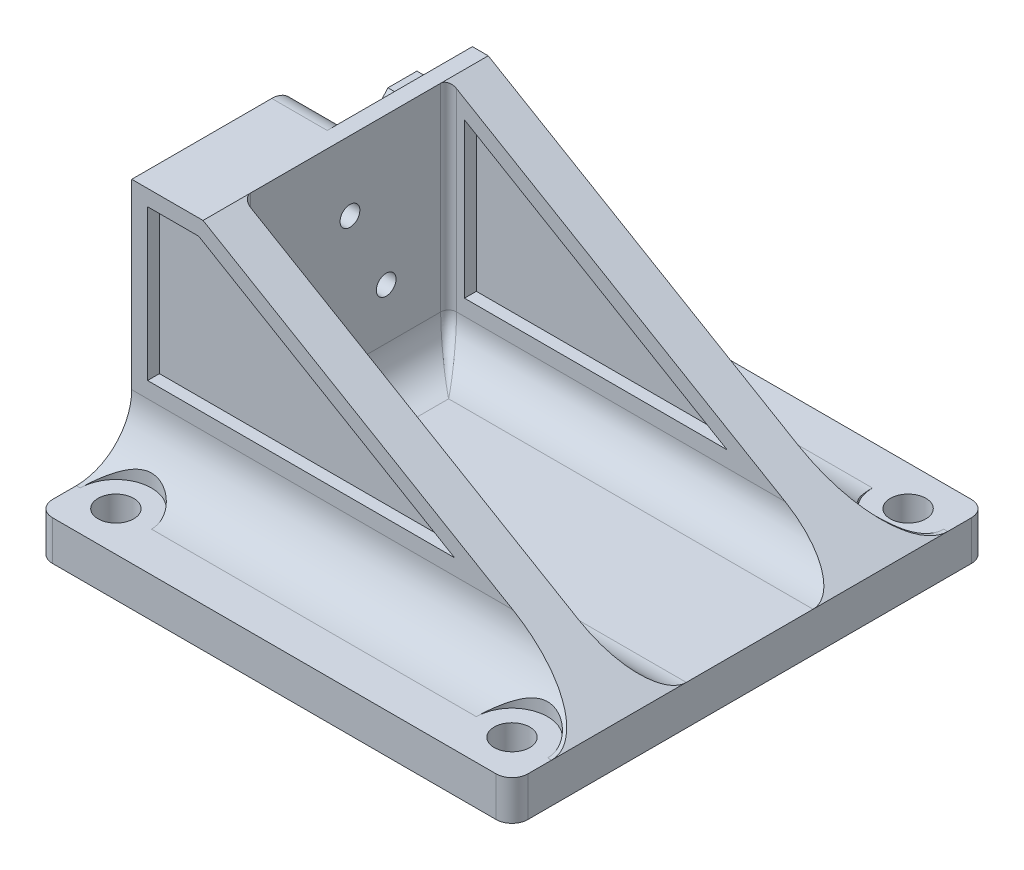
SolidWorks part; units mm, degrees
note: '?' marks a value the reader was unsure of.
ref_plane "Front Plane" through (0, 0, 0) normal (0, 0, 1) x (1, 0, 0)
ref_plane "Top Plane" through (0, 0, 0) normal (0, 1, 0) x (1, 0, 0)
ref_plane "Right Plane" through (0, 0, 0) normal (1, 0, 0) x (0, 0, -1)
sketch "Sketch2" plane through (0, 0, 0) normal (0, 1, 0) x (1, 0, 0)
  line L1 (-30, 30) -> (30, 30)
  line L2 (-30, 30) -> (-30, -30)
  line L3 (-30, -30) -> (30, -30)
  line L4 (30, 30) -> (30, -30)
  line L5 (-30, 30) -> (30, -30) construction
  line L6 (-30, -30) -> (30, 30) construction
  point P0 (0, 0)
  dimension "D1" = 60
  dimension "D2" = 60
extrude "Boss-Extrude1" add sketch "Sketch2" along normal blind 5 contours L2 L3 L4 L1
sketch "Sketch5" plane through (0, 5, 0) normal (0, 1, 0) x (1, 0, 0)
  line L0 (-30, 30) -> (-30, -30) construction
  line L1 (-30, -18) -> (-21, -18)
  line L2 (-30, -18) -> (-30, 18)
  line L3 (-30, 18) -> (-21, 18)
  line L4 (-21, -18) -> (-21, 18)
  line L5 (-30, 0) -> (37.4469, 0) construction
  line L6 (-2.75, 0) -> (2.75, 0) construction
  line L7 (-30, 30) -> (30, 30) construction
  dimension "D1" = 9
  dimension "D2" = 12
extrude "Boss-Extrude2" add sketch "Sketch5" along normal blind 30
sketch "Sketch6" plane through (0, 0, 18) normal (0, 0, 1) x (1, 0, 0)
  line L0 (-21, 35) -> (30, 5)
  line L1 (30, 5) -> (-21, 5)
  line L2 (-21, 5) -> (-21, 35)
extrude "Boss-Extrude3" add sketch "Sketch6" against normal blind 5
sketch "Sketch15" plane through (0, 0, -18) normal (0, 0, -1) x (-1, 0, 0)
  line L3 (21, 5) -> (21, 35)
  line L4 (21, 35) -> (-30, 5)
  line L5 (-30, 5) -> (21, 5)
  line L6 (21, 5) -> (21, 35)
  line L7 (21, 35) -> (-30, 5)
  line L8 (-30, 5) -> (21, 5)
  dimension "D1" = 0
extrude "Boss-Extrude4" add sketch "Sketch15" against normal blind 5
fillet "Fillet6" radius 7 2 edges at (0, 5, -18) (0, 5, 18)
hole_wizard "M4 Clearance Hole2" positions "Sketch3" profile "Sketch4" hole size "M4" standard "ANSI Metric" end condition through all
sketch "Sketch3" plane through (0, 5, 0) normal (0, 1, 0) x (1, 0, 0)
  line L1 (-25, -25) -> (25, -25) construction
  line L2 (-25, -25) -> (-25, 25) construction
  line L3 (-25, 25) -> (25, 25) construction
  line L4 (25, -25) -> (25, 25) construction
  line L5 (-25, -25) -> (25, 25) construction
  line L6 (-25, 25) -> (25, -25) construction
  point P2 (25, 25)
  point P105 (-25, -25)
  point P106 (-25, 25)
  point P107 (25, -25)
  dimension "D1" = 50
  dimension "D2" = 50
sketch "Sketch4" plane through (25, 5, -25) normal (1, 0, 0) x (0, 0, 1)
  line L0 (0, 0) -> (0, 5)
  line L1 (0, 5) -> (2.25, 5)
  line L2 (2.25, 5) -> (2.25, 0)
  line L5 (2.25, 0) -> (0, 0)
  line L11 (0, -6.35) -> (0, 107.95) construction
  dimension "Thru Hole Dia." = 4.5
  dimension "Thru Hole Depth" = 5
sketch "Sketch17" plane through (0, 5, 0) normal (0, 1, 0) x (1, 0, 0)
  line L28 (27.25, -25) -> (22.75, -25) construction
  line L29 (-22.75, -25) -> (-27.25, -25) construction
  line L30 (22.75, 25) -> (27.25, 25) construction
  circle A8 centre (25, -25) radius 4.5
  circle A9 centre (-25, -25) radius 4.5
  circle A10 centre (-25, 25) radius 4.5
  circle A11 centre (25, 25) radius 4.5
  dimension "D1" = 9
extrude "Cut-Extrude7" cut sketch "Sketch17" along normal blind 5
sketch "Sketch18" plane through (0, 0, 0) normal (0, -1, 0) x (1, 0, 0)
  line L48 (-28, 28) -> (-28, -28)
  line L49 (-28, -28) -> (28, -28)
  line L50 (28, 28) -> (-28, 28)
  line L51 (28, -28) -> (28, 28)
  line L52 (-28, 21.9896) -> (-28, -21.9896)
  line L53 (-21.9896, -28) -> (21.9896, -28)
  line L54 (21.9896, 28) -> (-21.9896, 28)
  line L55 (28, -21.9896) -> (28, 21.9896)
  circle A43 centre (25, 25) radius 4.25
  arc A44 (21.9896, 28) -> (28, 21.9896) centre (25, 25) ccw
  circle A46 centre (-25, 25) radius 4.25
  arc A47 (-28, 21.9896) -> (-21.9896, 28) centre (-25, 25) ccw
  circle A49 centre (25, -25) radius 4.25
  arc A50 (28, -21.9896) -> (21.9896, -28) centre (25, -25) ccw
  circle A52 centre (-25, -25) radius 4.25
  arc A53 (-21.9896, -28) -> (-28, -21.9896) centre (-25, -25) ccw
  point P15 (0, 0)
  dimension "D1" = 2
  dimension "D2" = 2
  dimension "D3" = 2
  dimension "D4" = 2
  dimension "D5" = 2
extrude "Cut-Extrude8" cut sketch "Sketch18" against normal blind 3
sketch "Sketch19" plane through (0, 0, 0) normal (0, -1, 0) x (1, 0, 0)
  line L0 (15.5, -28) -> (15.5, 28)
  line L3 (-21.9896, -28) -> (21.9896, -28) construction
  line L4 (-15.5, 28) -> (-15.5, -28)
  line L5 (21.9896, 28) -> (-21.9896, 28) construction
  line L6 (0, 0) -> (0, 35.3016) construction
  line L7 (0, -2.75) -> (0, 2.75) construction
  line L8 (28, -21.9896) -> (28, 21.9896) construction
  dimension "D1" = 12.5
rib "Rib9" sketch "Sketch19" sketch "Sketch19" thickness 3 extrusion direction normal to sketch draft on no parameters "D1"=3
fillet "Fillet7" radius 5 3 edges at (4.5, 5, -13) (4.5, 5, 13) (-21, 5, 0)
sketch "Sketch20" plane through (-21, 0, 0) normal (1, 0, 0) x (0, 0, -1)
  line L8 (-11, 33) -> (-11, 12)
  line L9 (-11, 12) -> (11, 12)
  line L10 (11, 12) -> (11, 33)
  line L11 (11, 33) -> (-11, 33)
  line L12 (-11, 33) -> (-11, 12)
  line L13 (-11, 12) -> (11, 12)
  line L14 (11, 12) -> (11, 33)
  line L15 (11, 33) -> (-11, 33)
  dimension "D1" = 2
extrude "Cut-Extrude9" [suppressed] cut sketch "Sketch20" against normal blind 2
sketch "Sketch21" plane through (0, 0, -13) normal (0, 0, 1) x (1, 0, 0)
  line L6 (-19, 31.5032) -> (-19, 12)
  line L7 (-19, 12) -> (14.1554, 12)
  line L8 (14.1554, 12) -> (-19, 31.5032)
  line L9 (-19, 31.5032) -> (-19, 12)
  line L10 (-19, 12) -> (14.1554, 12)
  line L11 (14.1554, 12) -> (-19, 31.5032)
  dimension "D1" = 2
extrude "Cut-Extrude10" cut sketch "Sketch21" against normal blind 1.5
sketch "Sketch22" plane through (0, 0, -18) normal (0, 0, -1) x (-1, 0, 0)
  line L4 (-10.7554, 14) -> (28, 14)
  line L6 (-10.7554, 14) -> (28, 14)
  line L9 (28, 14) -> (28, 33)
  line L10 (28, 33) -> (21.5446, 33)
  line L11 (21.5446, 33) -> (-10.7554, 14)
  line L13 (28, 14) -> (28, 33)
  line L14 (28, 33) -> (21.5446, 33)
  line L15 (21.5446, 33) -> (-10.7554, 14)
  dimension "D1" = 2
extrude "Cut-Extrude11" [suppressed] cut sketch "Sketch22" against normal blind 1.5
fillet "Fillet8" radius 1 4 edges at (-19.5355, 6.4645, 11.5355) (-19.5355, 6.4645, -11.5355) (-21, 22.5, 13) (-21, 22.5, -13)
mirror "Mirror3" about plane through (0, 0, 0) normal (0, 0, 1) of "Cut-Extrude11", "Cut-Extrude10"
sketch "Sketch23" plane through (-30, 0, 0) normal (1, 0, 0) x (0, 0, -1)
  line L0 (-11, 20) -> (11, 20) construction
  line L1 (33, 0) -> (-33, 0) construction
  line L3 (0, 20) -> (0.5447, 26.2262) construction
  line L4 (0, 19.25) -> (0, -19.25) construction
  circle A0 centre (0, 20) radius 6.25 construction
  circle A1 centre (0.5447, 26.2262) radius 1.25
  dimension "D2" = 12.5
  dimension "D3" = 2.5
  dimension "D1" = 5
  dimension "D4" = 20
ref_axis "Axis2" [suppressed] through (-30, 20, 0) along (1, 0, 0)?
extrude "Cut-Extrude12" cut sketch "Sketch23" along normal through all contours A1
pattern_circular "CirPattern2" count 3 over 360 about axis through (0, 20, 0) along (1, 0, 0) of "Cut-Extrude12"
fillet "Fillet9" [suppressed] radius 1
fillet "Fillet10" radius 2 4 edges at (-30, 2.5, 30) (-30, 2.5, -30) (30, 2.5, -30) (30, 2.5, 30)
sketch "Sketch24" plane through (-30, 0, 0) normal (-1, 0, 0) x (0, 0, 1)
  line L0 (0, -19.25) -> (0, 19.25) construction
  line L1 (0, 20) -> (18, 20) construction
  line L2 (18, 35) -> (18, 12) construction
  line L3 (33, 0) -> (-33, 0) construction
  circle A0 centre (0, 20) radius 8.875
  dimension "D1" = 17.75
  dimension "D2" = 20
extrude "Cut-Extrude13" cut sketch "Sketch24" against normal blind 7 contours A0
sketch "Sketch25" plane through (-30, 0, 0) normal (-1, 0, 0) x (0, 0, 1)
  line L0 (-1.4865, 28.7496) -> (-10.1514, 38.373)
  line L2 (-10.1514, 38.373) -> (-17.7922, 39.7602)
  line L3 (-17.7922, 39.7602) -> (-17.2113, 32.0163)
  line L5 (-17.2113, 32.0163) -> (-8.5463, 22.3929)
  line L6 (-8.5463, 22.3929) -> (-1.4865, 28.7496)
  line L7 (-17.7922, 39.7602) -> (0, 20) construction
  line L8 (0, -19.25) -> (0, 19.25) construction
  circle A0 centre (0, 20) radius 8.875 construction
  circle A1 centre (0, 20) radius 8.875 construction
  dimension "D1" = 42
  dimension "D2" = 9.5
extrude "Cut-Extrude14" cut sketch "Sketch25" against normal blind 7
fillet "Fillet11" radius 7 2 edges at (-26.5, 22.3929, -8.5463) (-26.5, 28.7496, -1.4865)
sketch "Sketch26" [suppressed] plane through (-30, 0, 0) normal (-1, 0, 0) x (0, 0, 1)
  line L0 (-16.5, 31.2263) -> (-18, 31.2263)
  line L1 (-18, 35) -> (-18, 12) construction
  line L2 (-18, 31.2263) -> (-18, 35)
  line L3 (-18, 35) -> (-12, 35)
  line L4 (-12, 35) -> (-12, 31.2263)
  line L5 (-12, 10) -> (-12, 35) construction
  line L6 (-12, 31.2263) -> (-16.5, 31.2263)
sketch "Sketch27" plane through (-30, 0, 0) normal (-1, 0, 0) x (0, 0, 1)
  line L0 (-18, 28.8304) -> (-18, 35)
  line L2 (-18, 35) -> (-13, 35)
  line L3 (-7.1143, 35) -> (-17.4351, 35) construction
  line L4 (-13, 35) -> (-13, 28.8304)
  line L5 (-13, 28.8304) -> (-18, 28.8304)
  line L7 (-13, 34.4118) -> (-13, 10) construction
extrude "Cut-Extrude17" cut sketch "Sketch27" against normal blind 7
sketch "Sketch28" plane through (0, 0, -18) normal (0, 0, -1) x (-1, 0, 0)
  line L12 (28, 14) -> (28, 26.8304)
  line L13 (28, 26.8304) -> (21, 26.8304)
  line L14 (21, 26.8304) -> (21, 32.6796)
  line L15 (21, 32.6796) -> (-10.7554, 14)
  line L16 (-10.7554, 14) -> (28, 14)
  line L17 (28, 14) -> (28, 26.8304)
  line L18 (28, 26.8304) -> (21, 26.8304)
  line L19 (21, 26.8304) -> (21, 32.6796)
  line L20 (21, 32.6796) -> (-10.7554, 14)
  line L21 (-10.7554, 14) -> (28, 14)
  dimension "D1" = 2
extrude "Cut-Extrude18" cut sketch "Sketch28" against normal blind 1.5
sketch "Sketch29" plane through (0, 0, 18) normal (0, 0, 1) x (1, 0, 0)
  line L8 (10.7554, 14) -> (-21.5446, 33)
  line L9 (-21.5446, 33) -> (-28, 33)
  line L10 (-28, 33) -> (-28, 14)
  line L11 (-28, 14) -> (10.7554, 14)
  line L12 (10.7554, 14) -> (-21.5446, 33)
  line L13 (-21.5446, 33) -> (-28, 33)
  line L14 (-28, 33) -> (-28, 14)
  line L15 (-28, 14) -> (10.7554, 14)
  dimension "D1" = 2
extrude "Cut-Extrude19" cut sketch "Sketch29" against normal blind 1.5
fillet "Fillet13" radius 3 1 edges at (-26.5, 35, -7.1143)
